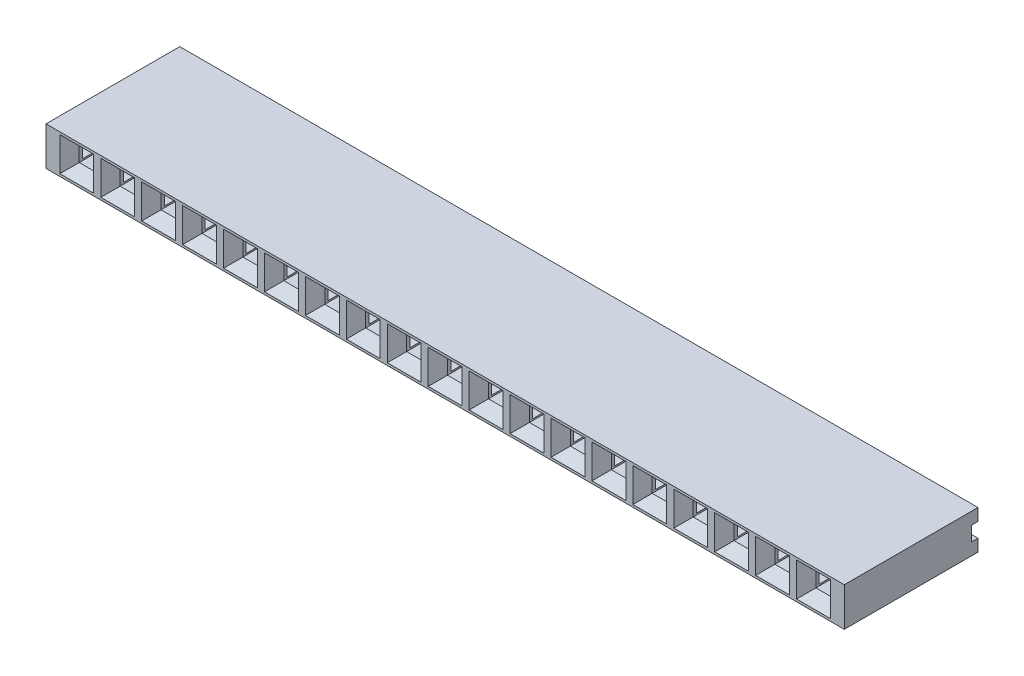
SolidWorks part; units mm, degrees
note: The reader was unsure of these and kept them because the rebuilt part matched: shared geometry of "Эскиз-БоковаяНакладка<2>".
other "Пластик"
ref_plane "Front Plane" through (0, 0, 0) normal (0, 0, 1) x (1, 0, 0)
ref_plane "Top Plane" through (0, 0, 0) normal (0, 1, 0) x (1, 0, 0)
ref_plane "Right Plane" through (0, 0, 0) normal (1, 0, 0) x (0, 0, -1)
sketch "Эскиз-ВнутреннееСечение" plane through (0, 0, 0) normal (0, 0, 1) x (1, 0, 0)
  line L0 (-1, 0.35) -> (-0.45, 0.35)
  line L1 (-1.27, -1.2) -> (1.27, -1.2)
  line L2 (-1.27, -1.2) -> (-1.27, 1.2)
  line L3 (-1.27, 1.2) -> (1.27, 1.2)
  line L4 (1.27, -1.2) -> (1.27, 1.2)
  line L5 (-1.27, -1.2) -> (1.27, 1.2) construction
  line L6 (-1.27, 1.2) -> (1.27, -1.2) construction
  line L8 (-1, -0.35) -> (-1, 0.35)
  line L9 (-0.45, 0.45) -> (0.45, 0.45)
  line L11 (0, 1.2) -> (0, -1.2) construction
  line L12 (0.45, 0.35) -> (0.45, 0.45)
  line L13 (-1.27, 0) -> (1.27, 0) construction
  line L14 (1, 0.35) -> (0.45, 0.35)
  line L15 (-0.45, 0.35) -> (-0.45, 0.45)
  line L16 (1, -0.35) -> (0.45, -0.35)
  line L17 (0.45, -0.35) -> (0.45, -0.45)
  line L18 (-0.45, -0.35) -> (-0.45, -0.45)
  line L19 (-1, -0.35) -> (-0.45, -0.35)
  line L20 (-0.45, -0.45) -> (0.45, -0.45)
  line L21 (1, -0.35) -> (1, 0.35)
  point P0 (0, 0)
  point P5 (0, 0)
  dimension "D1" = 2.4
  dimension "D2" = 2.54
  dimension "D3" = 1
  dimension "D4" = 0.35
  dimension "D5" = 0.1
  dimension "D7" = 0.55
extrude "Бобышка-ОтЦентраВверхВниз" add sketch "Эскиз-ВнутреннееСечение" against normal blind 0.4 and the other way blind 6.7 contours L8 L0 L15 L9 L12 L14 L21 L16 L17 L20 L18 L19
sketch "Эскиз-СамыйНиз" plane through (0, 0, -0.4) normal (0, 0, -1) x (-1, 0, 0)
  line L1 (1.27, 1.2) -> (1.27, -1.2) construction
  line L2 (-1.27, -1.2) -> (-1.27, 1.2) construction
  line L3 (0.45, -0.45) -> (-0.45, -0.45) construction
  line L4 (1.27, -1.2) -> (-1.27, -1.2)
  line L5 (1.27, -1.2) -> (1.27, -0.45)
  line L6 (1.27, -0.45) -> (-1.27, -0.45)
  line L7 (-1.27, -1.2) -> (-1.27, -0.45)
  line L9 (-1.27, 1.2) -> (1.27, 1.2)
  line L10 (-1.27, 1.2) -> (-1.27, 0.45)
  line L11 (-1.27, 0.45) -> (1.27, 0.45)
  line L12 (1.27, 1.2) -> (1.27, 0.45)
  line L13 (-0.45, 0.45) -> (0.45, 0.45) construction
  point P11 (0, 0)
extrude "Бобышка-СамыйНиз" add sketch "Эскиз-СамыйНиз" along normal blind 0.4
sketch "Эскиз-ВерхняяПеремычка" plane through (0, 0, 6.7) normal (0, 0, 1) x (1, 0, 0)
  line L1 (-1.27, 1.2) -> (1.27, 1.2)
  line L2 (-1.27, 1.2) -> (-1.27, -1.2)
  line L3 (-1.27, -1.2) -> (1.27, -1.2)
  line L4 (1.27, 1.2) -> (1.27, -1.2)
  line L5 (-0.45, -0.45) -> (0.45, -0.45)
  line L6 (-0.45, -0.45) -> (-0.45, 0.45)
  line L7 (-0.45, 0.45) -> (0.45, 0.45)
  line L8 (0.45, -0.45) -> (0.45, 0.45)
  line L9 (-0.45, -0.45) -> (0.45, 0.45) construction
  line L10 (-0.45, 0.45) -> (0.45, -0.45) construction
  point P4 (0, 0)
extrude "Бобышка-СамыйВерх" add sketch "Эскиз-ВерхняяПеремычка" along normal blind 0.8
chamfer "Фаска-СверхуВнутрь" distance 0.6 angle 45 4 edges at (0, -0.45, 7.5) (0.45, 0, 7.5) (0, 0.45, 7.5) (-0.45, 0, 7.5)
pattern_linear "Пластик_Массив" count 19 spacing 2.54 along (-1, 0, 0) of bodies 103
combine bodies "Соединить_Массив" operation type add bodies to combine 103 120 119 118 117 116 115 114 113 112 111 110 109 108 107 106 105 104 121
sketch "Эскиз-БоковаяНакладка" plane through (1.27, 0, 0) normal (1, 0, 0) x (0, 0, -1)
  line L1 (0.8, 1.2) -> (0.8, 0.45)
  line L2 (0.8, 0.45) -> (0.4, 0.45)
  line L3 (0.4, 0.45) -> (0.4, -0.45)
  line L4 (0.4, -0.45) -> (0.4, 0.45) construction
  line L5 (0.4, -0.45) -> (0.8, -0.45)
  line L6 (0.8, -0.45) -> (0.8, -1.2)
  line L7 (0.8, -1.2) -> (-7.5, -1.2)
  line L8 (-7.5, -1.2) -> (-7.5, 1.2)
  line L9 (-7.5, 1.2) -> (0.8, 1.2)
extrude "Бобышка-БоковаяНакладка1" add sketch "Эскиз-БоковаяНакладка" along normal blind 0.64 from surface at 0 starting at face at (1.27, 0, 1.375)
extrude "Бобышка-БоковаяНакладка2" add sketch "Эскиз-БоковаяНакладка<2>" against normal blind 0.64 from surface
sketch "Эскиз-БоковаяНакладка<2>" plane through (1.27, 0, 0) normal (1, 0, 0) x (0, 0, -1) same geometry as "Эскиз-БоковаяНакладка"
